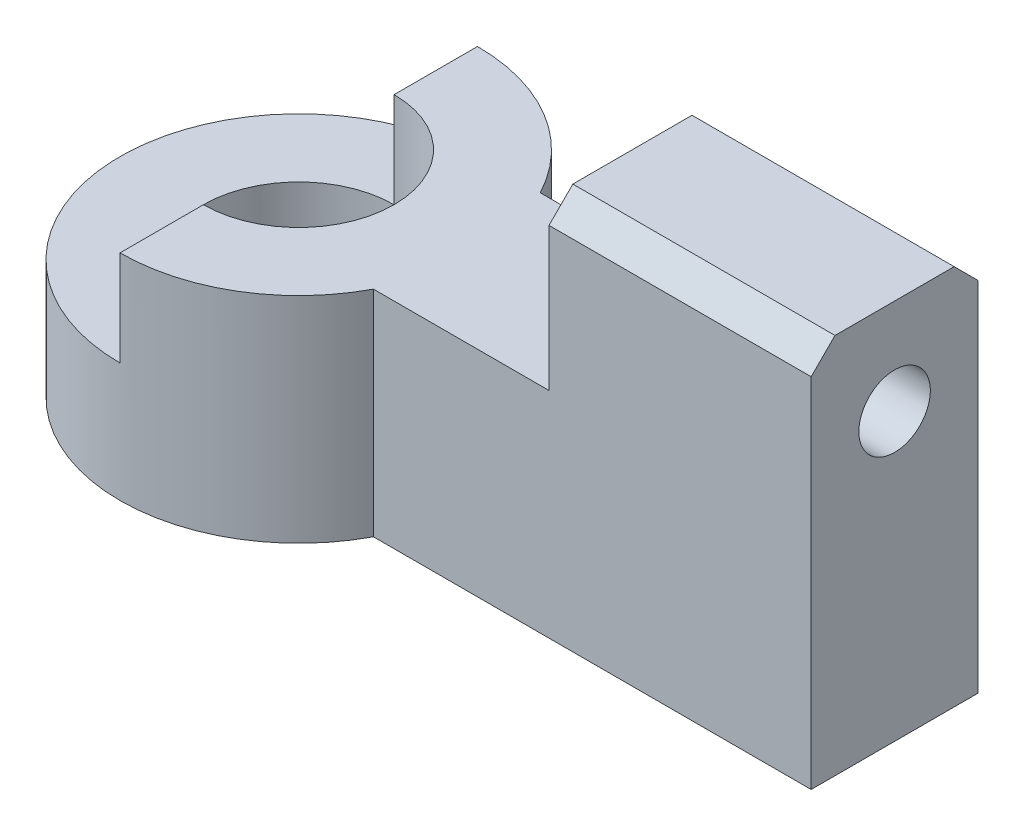
SolidWorks part; units mm, degrees
ref_plane "Front Plane" through (0, 0, 0) normal (0, 0, 1) x (1, 0, 0)
ref_plane "Top Plane" through (0, 0, 0) normal (0, 1, 0) x (1, 0, 0)
ref_plane "Right Plane" through (0, 0, 0) normal (1, 0, 0) x (0, 0, -1)
sketch "Sketch1" plane through (0, 0, 0) normal (0, 1, 0) x (1, 0, 0)
  line L0 (0, 0) -> (-15, 0) construction
  line L1 (13.2665, 7) -> (50, 7)
  line L4 (50, 7) -> (50, -7)
  line L5 (-14.8551, 2.0797) -> (50, -7) construction
  line L6 (-14.8551, -2.0797) -> (50, 7) construction
  line L7 (13.2665, -7) -> (50, -7)
  line L8 (0, -15) -> (0, 15)
  line L9 (28, 7) -> (28, -7)
  arc A0 (13.2665, 7) -> (13.2665, -7) centre (0, 0) ccw
  circle A1 centre (0, 0) radius 8
  point P13 (0, 0)
  dimension "D2" = 30
  dimension "D3" = 16
  dimension "D1" = 65
  dimension "D4" = 14
  dimension "D5" = 22
extrude "Boss-Extrude1" add sketch "Sketch1" along normal blind 10 contours A1 L8 A0 | A1 L8 A0 L7 L9 L1 | L1 L9 L7 L4 region at (13.4059, 0, 0) region at (39, 0, 0) region at (-0.3354, 0, -11.5)
extrude "Boss-Extrude2" add sketch "Sketch1<3>" along normal blind 18 contours A1 L8 A0 L7 L9 L1 | L1 L9 L7 L4 region at (13.4059, 0, 0) region at (39, 0, 0)
sketch "Sketch1<3>" plane through (0, 0, 0) normal (0, 1, 0) x (1, 0, 0) same geometry as "Sketch1"
extrude "Boss-Extrude3" add sketch "Sketch1<4>" along normal blind 32 contours L1 L9 L7 L4 region at (39, 0, 0)
sketch "Sketch1<4>" plane through (0, 0, 0) normal (0, 1, 0) x (1, 0, 0) same geometry as "Sketch1"
chamfer "Chamfer1" distance 2 angle 45 2 edges at (39, 32, -7) (39, 32, 7)
sketch "Sketch2" plane through (28, 0, 0) normal (-1, 0, 0) x (0, 0, 1)
  line L0 (-7, 30) -> (-7, 18) construction
  line L1 (-5, 32) -> (5, 32) construction
  circle A0 centre (0, 24) radius 3
  point P2 (0, 0)
  point P5 (-7, 24)
  point P8 (0, 32)
  dimension "D1" = 6
extrude "Cut-Extrude1" cut sketch "Sketch2" against normal through all
